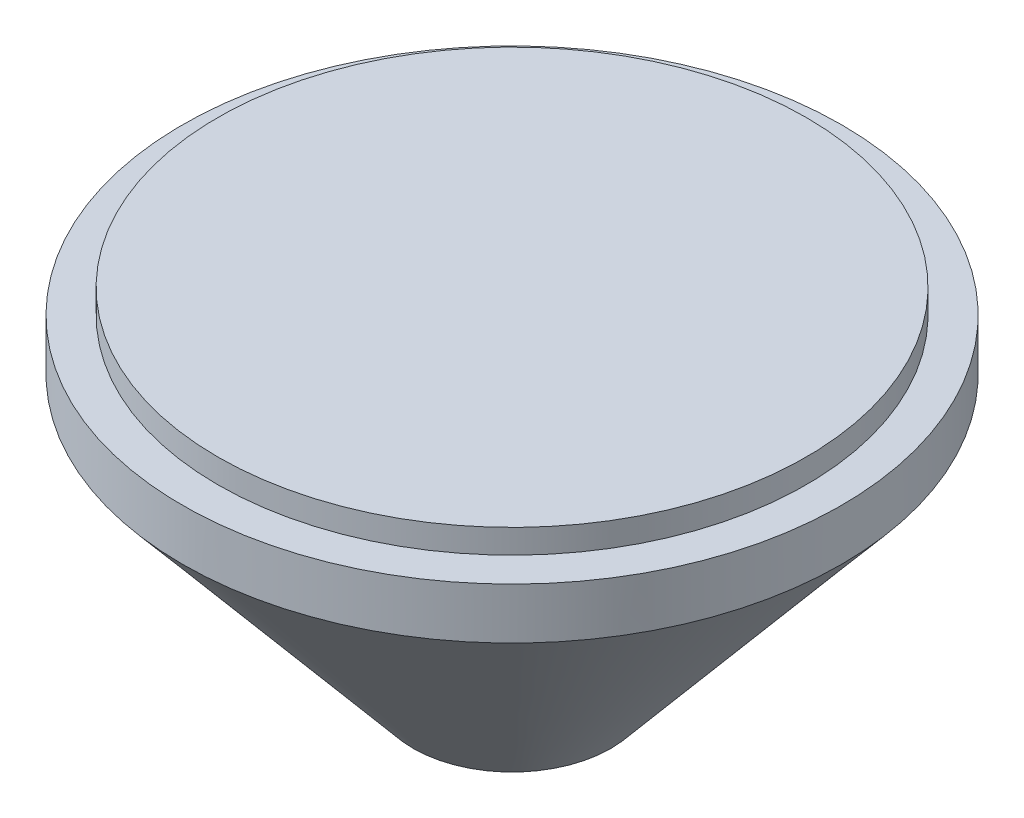
SolidWorks part; units mm, degrees
material "ABS PC"
ref_plane "Front Plane" through (0, 0, 0) normal (0, 0, 1) x (1, 0, 0)
ref_plane "Top Plane" through (0, 0, 0) normal (0, 1, 0) x (1, 0, 0)
ref_plane "Right Plane" through (0, 0, 0) normal (1, 0, 0) x (0, 0, -1)
sketch "Sketch1" plane through (0, 0, 0) normal (0, 1, 0) x (1, 0, 0)
  circle A0 centre (0, 0) radius 10
  dimension "D1" = 20
extrude "Boss-Extrude1" add sketch "Sketch1" along normal blind 10.62
sketch "Sketch2" plane through (0, 0, 0) normal (1, 0, 0) x (0, 0, -1)
  line L0 (0, 0) -> (0, 10.62) construction
  line L1 (-10, 0) -> (10, 0) construction
  line L2 (10, 10.62) -> (-10, 10.62) construction
  line L3 (0, 10.62) -> (8.925, 10.62)
  line L4 (8.925, 10.62) -> (8.925, 9.89)
  line L5 (8.925, 9.89) -> (10, 9.89)
  line L6 (10, 0) -> (10, 10.62) construction
  line L7 (10, 9.89) -> (10, 8.34)
  line L8 (10, 0) -> (10, 10.62) construction
  line L9 (10, 8.34) -> (3, 0)
  line L10 (11, 9.89) -> (11, 10.62)
  line L11 (11, 10.62) -> (8.925, 10.62)
  line L12 (3, 0) -> (11, 0)
  line L13 (11, 0) -> (11, 9.89)
  line L14 (11, 9.89) -> (8.925, 9.89)
  dimension "D1" = 8.925
  dimension "D2" = 0.73
  dimension "D3" = 1.55
  dimension "D4" = 3
  dimension "D5" = 11
revolve "Cut-Revolve1" cut sketch "Sketch2" angle 360 about L0 region at (0, 10.255, -9.9625) region at (0, 3.3279, -8.3837)
sketch "Sketch3" plane through (0, 0, 0) normal (0, -1, 0) x (1, 0, 0)
  circle A0 centre (0, 0) radius 3
  dimension "D1" = 6
extrude "Cut-Extrude1" cut sketch "Sketch3" against normal blind 5 draft 2.25
dome "Dome1" faces to dome 1 distance 1 reverse direction no elliptical dome no face at (0, 5, -2.8035) parameters "D1"=1
